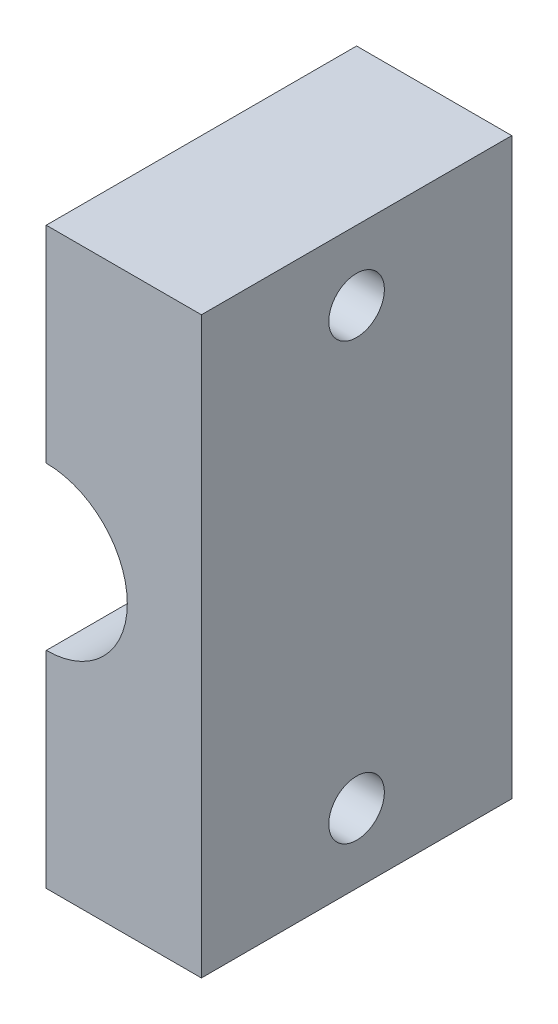
SolidWorks part; units mm, degrees
note: The reader was unsure of these and kept them because the rebuilt part matched: shared geometry of "草图1<4>", "草图1<5>".
ref_plane "前视基准面" through (0, 0, 0) normal (0, 0, 1) x (1, 0, 0)
ref_plane "上视基准面" through (0, 0, 0) normal (0, 1, 0) x (1, 0, 0)
ref_plane "右视基准面" through (0, 0, 0) normal (1, 0, 0) x (0, 0, -1)
other "Configuration Table"
sketch "草图1" plane through (0, 0, 0) normal (0, 0, 1) x (1, 0, 0)
  line L5 (0, 6.2) -> (3.35, 6.2)
  line L6 (0, 6.2) -> (0, -6.2)
  line L11 (0, -6.2) -> (3.35, -6.2)
  line L12 (3.35, 6.2) -> (3.35, -6.2)
  circle A0 centre (0, 0) radius 3.2
  point P6 (0, 0)
  point P7 (0, 0)
  point P8 (0, 0)
  dimension "D1" = 6.4
  dimension "D2" = 12.4
  dimension "D3" = 3.35
extrude "凸台-拉伸1" add sketch "草图1" along normal blind 2.7 contours A0 L6 L11 L12 L5
extrude "凸台-拉伸2" add sketch "草图1<4>" against normal blind 2 contours L5 L12 L11 L6
sketch "草图1<4>" plane through (0, 0, 0) normal (0, 0, 1) x (1, 0, 0) same geometry as "草图1"
extrude "凸台-拉伸3" add sketch "草图1<5>" along normal blind 2 from surface at 2.7 contours L5 L12 L11 L6 starting at face at (1.65, 0, 2.7)
sketch "草图1<5>" plane through (0, 0, 0) normal (0, 0, 1) x (1, 0, 0) same geometry as "草图1"
sketch "草图2" plane through (0, 0, 4.7) normal (0, 0, 1) x (1, 0, 0)
  line L0 (0, -6.2) -> (0, 6.2) construction
  circle A0 centre (0, 0) radius 1.75
  dimension "D1" = 3.5
extrude "切除-拉伸1" cut sketch "草图2" against normal through all
sketch "草图4" plane through (3.35, 0, 0) normal (1, 0, 0) x (0, 0, -1)
  line L0 (-1.35, 6.2) -> (-1.35, 4.7) construction
  line L3 (-4.7, 6.2) -> (2, 6.2) construction
  line L4 (-1.35, 4.7) -> (-1.35, -4.7) construction
  line L5 (-1.35, -4.7) -> (-1.35, -6.2) construction
  line L6 (-4.7, -6.2) -> (2, -6.2) construction
  circle A0 centre (-1.35, -4.7) radius 0.6
  circle A1 centre (-1.35, 4.7) radius 0.6
  dimension "D2" = 1.2
  dimension "D1" = 1.5
extrude "切除-拉伸2" cut sketch "草图4" against normal through all
